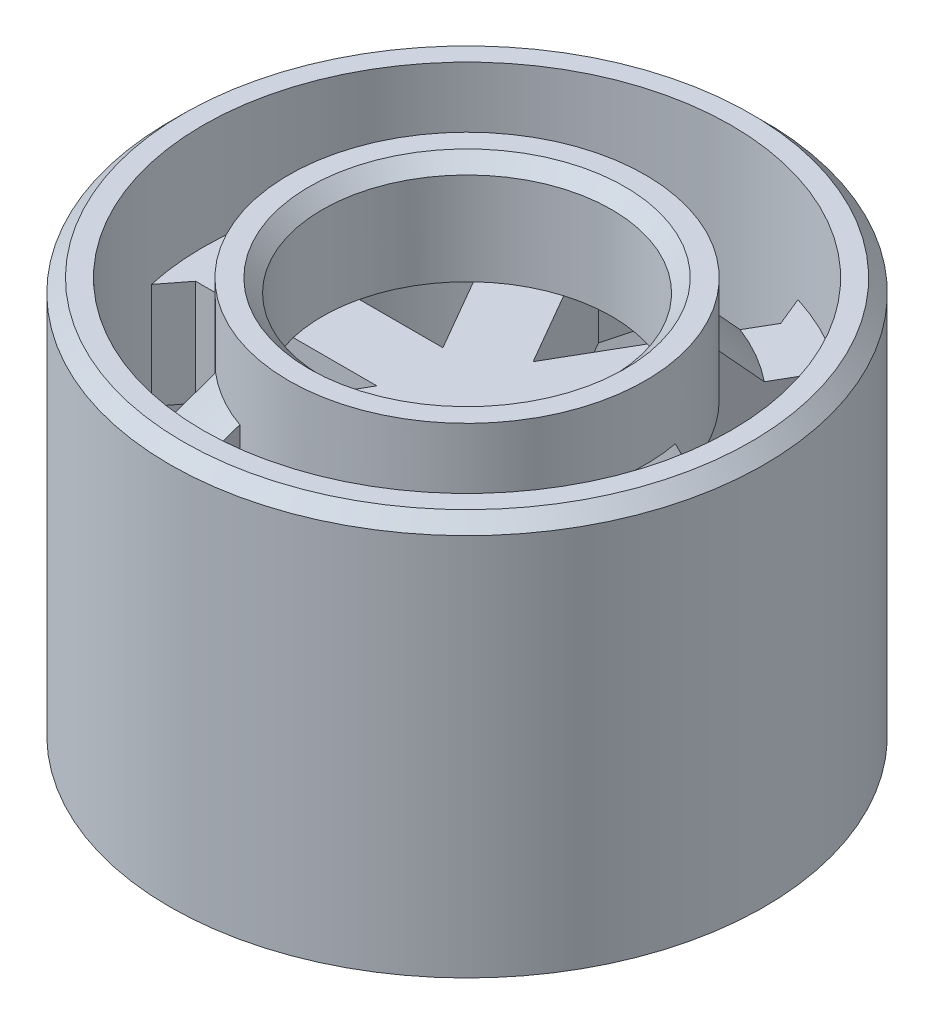
SolidWorks part; units mm, degrees
material "ABS"
ref_plane "Front Plane" through (0, 0, 0) normal (0, 0, 1) x (1, 0, 0)
ref_plane "Top Plane" through (0, 0, 0) normal (0, 1, 0) x (1, 0, 0)
ref_plane "Right Plane" through (0, 0, 0) normal (1, 0, 0) x (0, 0, -1)
sketch "Sketch1" plane through (0, 0, 0) normal (0, 1, 0) x (1, 0, 0)
  circle A0 centre (0, 0) radius 20
  circle A1 centre (0, 0) radius 22.5
  dimension "D1" = 40
  dimension "D2" = 45
extrude "Boss-Extrude1" add sketch "Sketch1" along normal blind 30
ref_plane "Plane1" through (0, 18, 0) normal (0, 1, 0) x (1, 0, 0)
sketch "Sketch2" plane through (0, 18, 0) normal (0, 1, 0) x (1, 0, 0)
  line L0 (-4.3301, 2.5) -> (-12.0866, 15.9347)
  line L1 (0, 5) -> (-7.7565, 18.4347)
  line L2 (0, 5) -> (7.7565, 18.4347)
  line L3 (4.3301, 2.5) -> (12.0866, 15.9347)
  line L4 (4.3301, 2.5) -> (19.8431, 2.5)
  line L5 (4.3301, -2.5) -> (19.8431, -2.5)
  line L6 (4.3301, -2.5) -> (12.0866, -15.9347)
  line L7 (0, -5) -> (7.7565, -18.4347)
  line L8 (0, -5) -> (-7.7565, -18.4347)
  line L9 (-4.3301, -2.5) -> (-12.0866, -15.9347)
  line L10 (-4.3301, -2.5) -> (-19.8431, -2.5)
  line L11 (-4.3301, 2.5) -> (-19.8431, 2.5)
  circle A1 centre (0, 0) radius 5 construction
  circle A2 centre (0, 0) radius 20 construction
  circle A3 centre (0, 0) radius 20
  point P33 (0, 0)
  dimension "D1" = 10
  dimension "D2" = 5
  dimension "D3" = 5
other "Pen Sketch1" parameters "D1"=7.7724, "D2"=2.8749, "D3"=9.1367, "D4"=6
extrude "Boss-Extrude2" add sketch "Sketch2" along normal mid plane 8 contours L7 A3 L6 L5 L4 L3 L2 L1 L0 L11 L10 L9 L8
chamfer "Chamfer1" distance 2 angle 45 12 edges at (-12.0866, 18, 15.9347) (-19.8431, 18, 2.5) (7.7565, 18, 18.4347) (12.0866, 18, 15.9347) (19.8431, 18, -2.5) (-7.7565, 18, 18.4347) (-19.8431, 18, -2.5) (-12.0866, 18, -15.9347) (12.0866, 18, -15.9347) (19.8431, 18, 2.5) (7.7565, 18, -18.4347) (-7.7565, 18, -18.4347)
sketch "Sketch4" plane through (0, 22, 0) normal (0, 1, 0) x (1, 0, 0)
  line L6 (-0.8968, 1.075) -> (-0.8975, 0.8333)
  line L7 (-0.8975, 0.8333) -> (-0.9024, -0.828)
  line L8 (-0.9024, -0.828) -> (-0.9032, -1.0697)
  arc A2 (-0.9032, -1.0697) -> (-0.8968, 1.075) centre (0, 0) ccw
extrude "Cut-Extrude1" cut sketch "Sketch4" against normal through all both and the other way through all
sketch "Sketch5" plane through (0, 22, 0) normal (0, 1, 0) x (1, 0, 0)
  line L0 (-0.8968, 1.075) -> (-0.9032, -1.0697) construction
  line L1 (-0.8968, 1.075) -> (-0.9032, -1.0697)
  arc A0 (-0.9032, -1.0697) -> (-0.8968, 1.075) centre (0, 0) ccw construction
  arc A1 (-0.9032, -1.0697) -> (-0.8968, 1.075) centre (0, 0) ccw
extrude "Boss-Extrude3" add sketch "Sketch5" against normal blind 1.5
sketch "Sketch6" plane through (0, 22, 0) normal (0, 1, 0) x (1, 0, 0)
  circle A0 centre (0, 0) radius 10.95
  circle A1 centre (0, 0) radius 13.5
  dimension "D1" = 21.9
  dimension "D2" = 27
extrude "Boss-Extrude4" add sketch "Sketch6" along normal up to surface (8 mm away) up to face at (0, 30, 22.5)
chamfer "Chamfer2" distance 1 angle 45 1 edges at (0, 30, 22.5)
chamfer "Chamfer3" distance 1 angle 45 1 edges at (0, 30, 10.95)
chamfer "Chamfer4" distance 2.5 angle 45 6 edges at (-6.75, 22, 11.6913) (-13.5, 22, 0) (-6.75, 22, -11.6913) (6.75, 22, 11.6913) (13.5, 22, 0) (6.75, 22, -11.6913)
